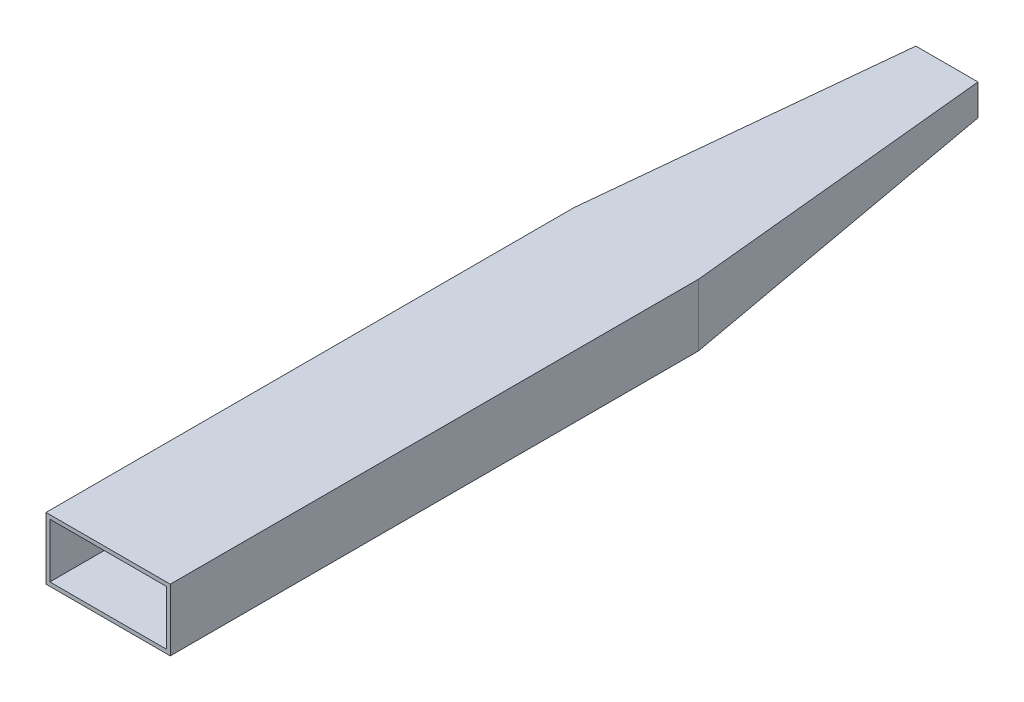
SolidWorks part; units mm, degrees
ref_plane "Front Plane" through (0, 0, 0) normal (0, 0, 1) x (1, 0, 0)
ref_plane "Top Plane" through (0, 0, 0) normal (0, 1, 0) x (1, 0, 0)
ref_plane "Right Plane" through (0, 0, 0) normal (1, 0, 0) x (0, 0, -1)
sketch "Sketch1" plane through (0, 0, 0) normal (0, 0, 1) x (1, 0, 0)
  line L5 (-50.8, -25.4) -> (50.8, -25.4)
  line L6 (-50.8, -25.4) -> (-50.8, 25.4)
  line L7 (-50.8, 25.4) -> (50.8, 25.4)
  line L8 (50.8, -25.4) -> (50.8, 25.4)
  line L9 (-50.8, -25.4) -> (50.8, 25.4) construction
  line L10 (-50.8, 25.4) -> (50.8, -25.4) construction
  point P6 (0, 0)
  dimension "D1" = 101.6
  dimension "D2" = 50.8
extrude "Boss-Extrude1" add sketch "Sketch1" against normal blind 431.8
ref_plane "Beginning of Tail" through (0, 0, -431.8) normal (0, 0, -1) x (-1, 0, 0)
ref_plane "End of Tail" through (0, 0, -685.8) normal (0, 0, -1) x (-1, 0, 0)
sketch "Sketch2" plane through (0, 0, -431.8) normal (0, 0, 1) x (1, 0, 0)
  line L8 (50.8, -25.4) -> (50.8, 25.4)
  line L9 (50.8, 25.4) -> (-50.8, 25.4)
  line L10 (-50.8, 25.4) -> (-50.8, -25.4)
  line L11 (-50.8, -25.4) -> (50.8, -25.4)
  line L12 (50.8, -25.4) -> (50.8, 25.4)
  line L13 (50.8, 25.4) -> (-50.8, 25.4)
  line L14 (-50.8, 25.4) -> (-50.8, -25.4)
  line L15 (-50.8, -25.4) -> (50.8, -25.4)
  point P7 (137.3688, 80.4936)
  dimension "D3" = 0
sketch "Sketch3" plane through (0, 0, -685.8) normal (0, 0, -1) x (-1, 0, 0)
  line L1 (-25.4, 0) -> (25.4, 0)
  line L2 (-25.4, 0) -> (-25.4, 25.4)
  line L3 (-25.4, 25.4) -> (25.4, 25.4)
  line L4 (25.4, 0) -> (25.4, 25.4)
  point P4 (-27.3734, -3.7342)
  point P5 (0, 0)
  point P9 (-25.4, 25.4)
  dimension "D1" = 25.4
  dimension "D2" = 50.8
loft "Loft1" add profiles "Sketch2", "Sketch3" connector at (-50.8, -25.4, -431.8) connector at (-25.4, 0, -685.8)
shell "Shell1" thickness 3.175 removed face at (0, 12.7, -685.8) removed face at (0, 0, 0)
